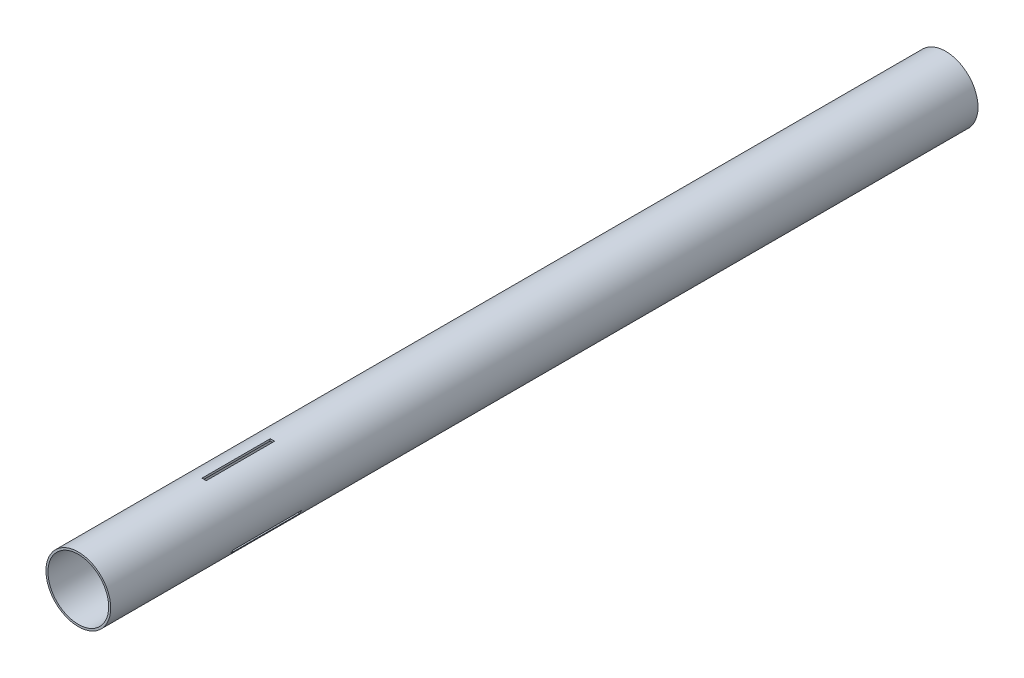
SolidWorks part; units mm, degrees
ref_plane "Front Plane" through (0, 0, 0) normal (0, 0, 1) x (1, 0, 0)
ref_plane "Top Plane" through (0, 0, 0) normal (0, 1, 0) x (1, 0, 0)
ref_plane "Right Plane" through (0, 0, 0) normal (1, 0, 0) x (0, 0, -1)
sketch "Sketch1" plane through (0, 0, 0) normal (0, 0, 1) x (1, 0, 0)
  circle A0 centre (0, 0) radius 23.6982
  circle A1 centre (0, 0) radius 22.225
  dimension "D1" = 47.3964
  dimension "D2" = 44.45
extrude "Boss-Extrude1" add sketch "Sketch1" along normal blind 635
ref_plane "Plane1" through (0, 100, 0) normal (0, 1, 0) x (1, 0, 0)
sketch "Sketch2" plane through (0, 100, 0) normal (0, 1, 0) x (1, 0, 0)
  line L3 (1.5875, -542.925) -> (1.5875, -492.887)
  line L4 (-1.5875, -542.925) -> (-1.5875, -492.887)
  line L5 (-1.5875, -492.887) -> (1.5875, -492.887)
  line L6 (-1.5875, -542.925) -> (1.5875, -542.925)
extrude "Cut-Extrude1" cut sketch "Sketch2" against normal up to next
pattern_circular "CirPattern2" count 3 over 360 about axis through (0, 0, 635) along (0, 0, 1) of "Cut-Extrude1"
